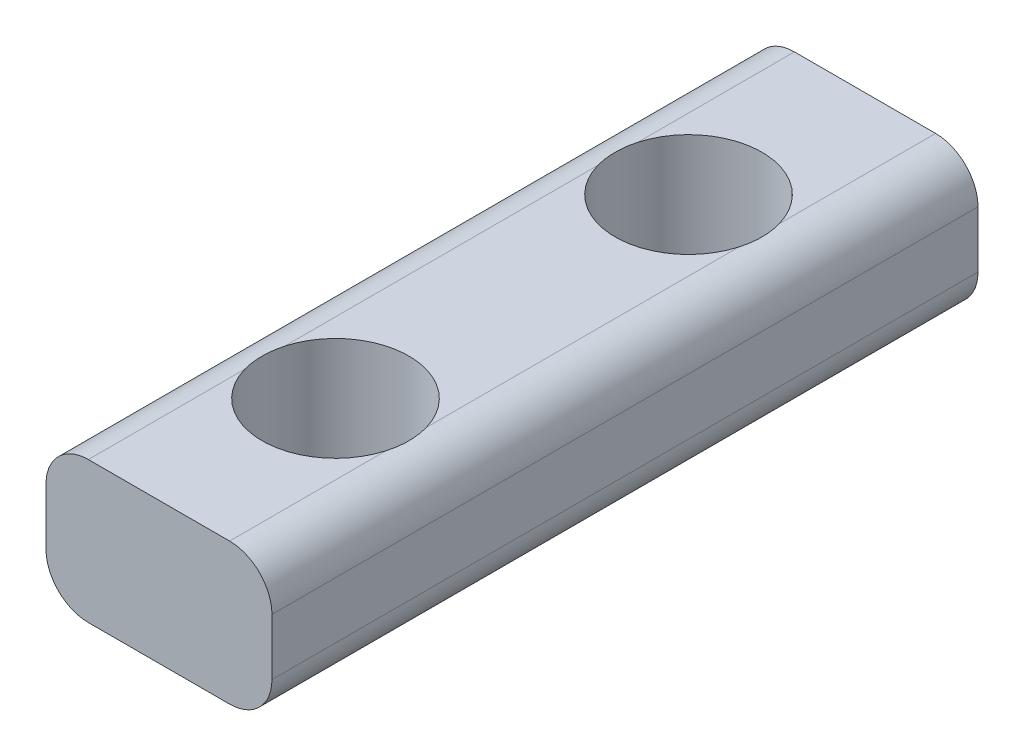
SolidWorks part; units mm, degrees
material "Plain Carbon Steel"
ref_plane "Front Plane" through (0, 0, 0) normal (0, 0, 1) x (1, 0, 0)
ref_plane "Top Plane" through (0, 0, 0) normal (0, 1, 0) x (1, 0, 0)
ref_plane "Right Plane" through (0, 0, 0) normal (1, 0, 0) x (0, 0, -1)
sketch "Sketch1" plane through (0, 0, 0) normal (0, 0, 1) x (1, 0, 0)
  line L1 (1.905, 0) -> (8.255, 0)
  line L2 (0, 1.905) -> (0, 4.445)
  line L3 (1.905, 6.35) -> (8.255, 6.35)
  line L4 (10.16, 1.905) -> (10.16, 4.445)
  arc A0 (8.255, 0) -> (10.16, 1.905) centre (8.255, 1.905) ccw
  arc A1 (1.905, 0) -> (0, 1.905) centre (1.905, 1.905) cw
  arc A2 (8.255, 6.35) -> (10.16, 4.445) centre (8.255, 4.445) cw
  arc A3 (0, 4.445) -> (1.905, 6.35) centre (1.905, 4.445) cw
  point P7 (10.16, 0)
  point P10 (0, 0)
  point P15 (0, 6.35)
  dimension "D3" = 1.905
  dimension "D4" = 1.905
  dimension "D1" = 10.16
  dimension "D2" = 6.35
extrude "Boss-Extrude1" add sketch "Sketch1" along normal blind 31.75
sketch "Sketch2" plane through (0, 6.35, 0) normal (0, 1, 0) x (1, 0, 0)
  line L0 (5.08, 0) -> (5.08, -31.75) construction
  line L1 (8.255, 0) -> (1.905, 0) construction
  line L2 (8.255, -31.75) -> (1.905, -31.75) construction
  circle A0 centre (5.08, -7.9375) radius 3.302
  circle A1 centre (5.08, -23.8125) radius 3.302
  dimension "D1" = 6.604
  dimension "D2" = 6.604
  dimension "D3" = 15.875
  dimension "D4" = 7.9375
extrude "Cut-Extrude1" cut sketch "Sketch2" against normal blind 31.75
